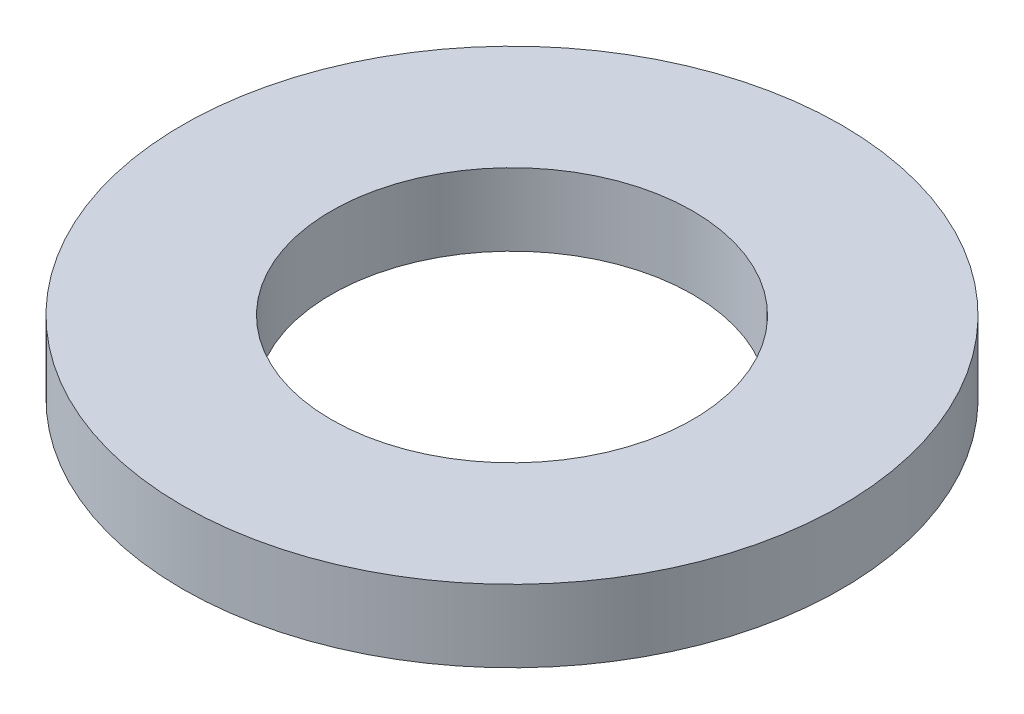
SolidWorks part; units mm, degrees
ref_plane "Front Plane" through (0, 0, 0) normal (0, 0, 1) x (1, 0, 0)
ref_plane "Top Plane" through (0, 0, 0) normal (0, 1, 0) x (1, 0, 0)
ref_plane "Right Plane" through (0, 0, 0) normal (1, 0, 0) x (0, 0, -1)
sketch "Sketch1" plane through (0, 0, 0) normal (0, 1, 0) x (1, 0, 0)
  circle A0 centre (0, 0) radius 77.5
  dimension "FLANGE_OD" = 155
extrude "Boss-Extrude1" add sketch "Sketch1" along normal blind 17
sketch "Sketch2" plane through (0, 0, 0) normal (0, 1, 0) x (1, 0, 0)
  circle A0 centre (0, 0) radius 42.5
  dimension "BORE_D" = 85
extrude "Cut-Extrude1" cut sketch "Sketch2" along normal through all
sketch "Sketch3" plane through (0, 17, 0) normal (0, 1, 0) x (1, 0, 0)
  circle A0 centre (0, 0) radius 25.7413 construction
  circle A1 centre (-25.7413, 0) radius 3.7783
  dimension "BOLT_D" = 7.5566
  dimension "BOLT_PCD" = 51.4827
extrude "Cut-Extrude2" cut sketch "Sketch3" against normal blind 10.2527 rebuild error yes
pattern_circular "CirPattern1" count 4 over 360 rebuild error yes
